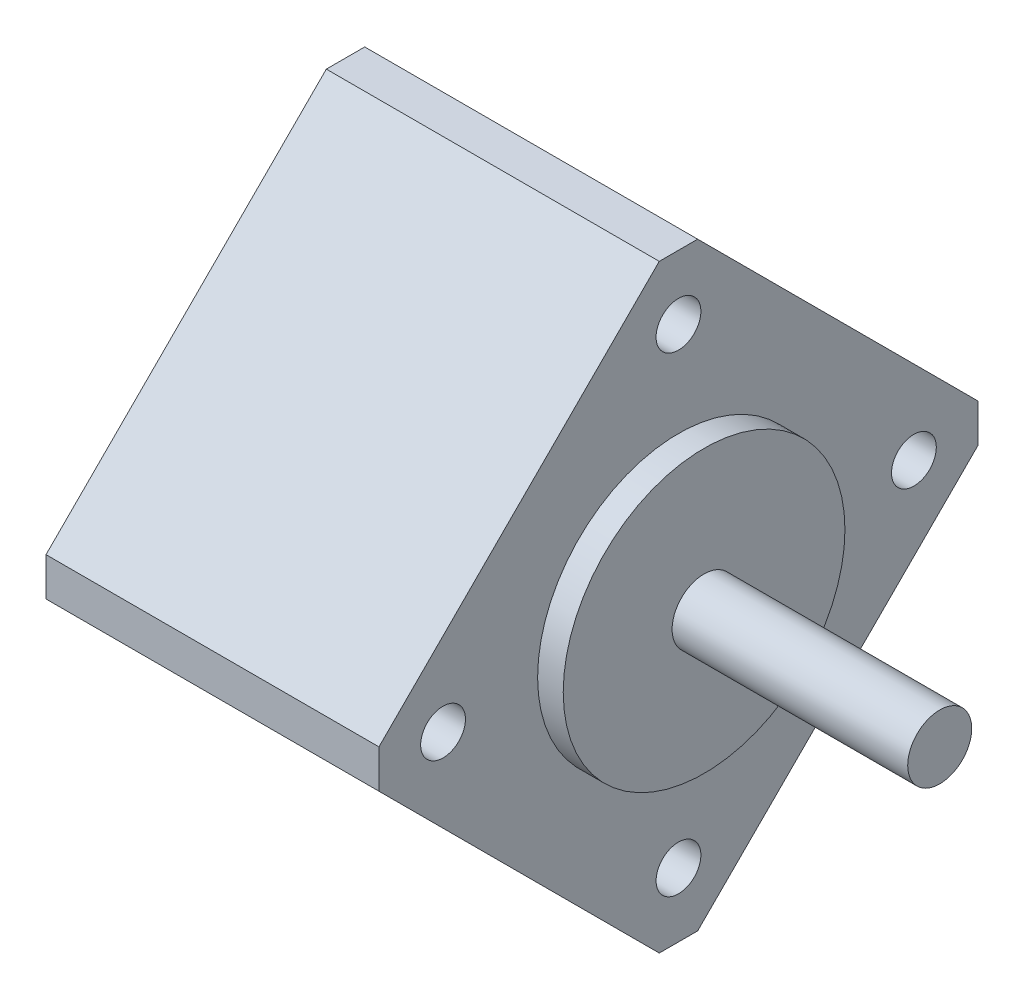
SolidWorks part; units mm, degrees
ref_plane "Front Plane" through (0, 0, 0) normal (0, 0, 1) x (1, 0, 0)
ref_plane "Top Plane" through (0, 0, 0) normal (0, 1, 0) x (1, 0, 0)
ref_plane "Right Plane" through (0, 0, 0) normal (1, 0, 0) x (0, 0, -1)
sketch "Sketch1" plane through (0, 0, 0) normal (0, 0, 1) x (1, 0, 0)
  line L0 (0, 0) -> (58.591, 0) construction
  line L2 (0, 0) -> (18.4, 0)
  line L3 (0, 0) -> (0, 2.5)
  line L4 (0, 2.5) -> (18.4, 2.5)
  line L5 (18.4, 0) -> (18.4, 2.5)
  line L6 (6, 2.5) -> (6, 6)
  line L11 (6, 6) -> (9.97, 6)
  line L16 (12.97, 6) -> (12.97, 3)
  line L17 (12.97, 3) -> (13.6304, 3)
  line L18 (13.6304, 3) -> (13.6304, 2.5)
  line L19 (13.6304, 2.5) -> (6, 2.5)
  line L22 (13.6304, 2.5) -> (16.1104, 2.5)
  line L23 (13.6304, 2.5) -> (13.6304, 4)
  line L24 (13.6304, 4) -> (16.1104, 4)
  line L25 (16.1104, 2.5) -> (16.1104, 4)
  line L27 (6, 6) -> (9.97, 6)
  line L28 (6, 6) -> (6, 9)
  line L29 (6, 9) -> (9.97, 9)
  line L30 (9.97, 6) -> (9.97, 9)
  line L31 (6, 9) -> (6, 8.25)
  line L32 (6, 8.25) -> (5, 8.25)
  line L33 (8.58, 22.001) -> (8.58, 12.476) construction
  line L34 (5, 12.476) -> (12.16, 12.476)
  line L35 (9.97, 9) -> (12.16, 9)
  line L36 (5, 7.5) -> (3, 7.5)
  line L37 (5, 8.25) -> (5, 12.476)
  line L38 (5, 7.5) -> (5, 14)
  line L39 (5, 14) -> (3, 14)
  line L40 (3, 7.5) -> (3, 14)
  line L41 (5, 22.001) -> (12.16, 22.001)
  line L42 (5, 22.001) -> (5, 30.1625)
  line L43 (5, 30.1625) -> (12.16, 30.1625)
  line L44 (12.16, 22.001) -> (12.16, 30.1625)
  line L49 (16.6304, 22.001) -> (16.6304, 7.5)
  line L51 (23.0104, 7.5) -> (23.0104, 6.5)
  line L54 (16.1104, 4) -> (13.6304, 4)
  line L56 (18.0304, 7.5) -> (23.0104, 7.5)
  line L57 (13.16, 22.001) -> (16.6304, 22.001)
  line L58 (16.1104, 3.5) -> (20.0104, 3.5)
  line L59 (29.9004, 14) -> (26.9004, 11)
  line L60 (4, 31.75) -> (18.0304, 31.75)
  line L61 (18.0304, 7.5) -> (23.0104, 7.5)
  line L62 (18.0304, 7.5) -> (18.0304, 12)
  line L63 (18.0304, 12) -> (23.0104, 12)
  line L64 (23.0104, 7.5) -> (23.0104, 12)
  line L65 (18.0304, 31.75) -> (18.0304, 12)
  line L66 (23.0104, 11) -> (26.9004, 11)
  line L67 (34.8004, 23) -> (31.3004, 19.5)
  line L68 (35.8004, 31) -> (38.7904, 33.99)
  line L69 (29.9004, 14) -> (29.9004, 15)
  line L70 (29.9004, 15) -> (22.9304, 15)
  line L71 (22.9304, 15) -> (21.0304, 15)
  line L72 (18.0304, 7.5) -> (16.6304, 7.5)
  line L73 (21.0304, 15) -> (21.0304, 43)
  line L74 (20.0304, 40) -> (10.0704, 40)
  line L75 (10.0704, 40) -> (4, 40)
  line L76 (21.0304, 43) -> (20.0304, 43)
  line L77 (22.9304, 15) -> (29.9004, 15)
  line L78 (22.9304, 15) -> (22.9304, 21)
  line L79 (22.9304, 21) -> (29.9004, 21)
  line L80 (29.9004, 15) -> (29.9004, 21)
  line L81 (10.0704, 40) -> (20.0304, 40)
  line L82 (10.0704, 40) -> (10.0704, 50)
  line L83 (10.0704, 50) -> (20.0304, 50)
  line L84 (20.0304, 40) -> (20.0304, 50)
  line L85 (4, 40) -> (4, 31.75)
  line L86 (12.97, 3) -> (12.97, 2.5)
  line L87 (31.3004, 19.5) -> (29.9004, 19.5)
  line L88 (21.51, 63.5) -> (21.51, 44)
  line L89 (21.51, 63.5) -> (25.9304, 63.5)
  line L90 (25.9304, 63.5) -> (25.9304, 25)
  line L91 (27.8304, 25) -> (25.9304, 25)
  line L92 (10.0704, 48) -> (9, 48)
  line L93 (9, 48) -> (9, 53.476)
  line L94 (9, 53.476) -> (20.0304, 53.476)
  line L95 (20.0304, 53.476) -> (20.0304, 50)
  line L96 (14.5152, 63.001) -> (14.5152, 53.476) construction
  line L97 (9, 63.001) -> (20.0304, 63.001)
  line L98 (9, 63.001) -> (9, 68.2625)
  line L99 (9, 68.2625) -> (20.0304, 68.2625)
  line L100 (20.0304, 63.001) -> (20.0304, 68.2625)
  line L101 (12.97, 6) -> (11.97, 6)
  line L102 (9, 42.5) -> (5, 42.5)
  line L103 (9, 42.5) -> (9, 55)
  line L104 (9, 55) -> (5, 55)
  line L105 (5, 42.5) -> (5, 55)
  line L106 (9.97, 6) -> (10.87, 6)
  line L107 (27.8304, 25) -> (34.8004, 25)
  line L108 (34.8004, 25) -> (34.8004, 23)
  line L109 (0, 0) -> (-2, 0)
  line L110 (0, 0) -> (0, 11)
  line L111 (27.8304, 25) -> (34.8004, 25)
  line L112 (27.8304, 25) -> (27.8304, 32.5)
  line L113 (27.8304, 32.5) -> (34.8004, 32.5)
  line L114 (34.8004, 25) -> (34.8004, 32.5)
  line L115 (35.8004, 31) -> (34.8004, 31)
  line L116 (27.8304, 32.5) -> (27.8304, 64.5)
  line L117 (21.1827, 74.025) -> (6.8477, 74.025)
  line L118 (6.8477, 74.025) -> (6.8477, 76.2)
  line L119 (38.7904, 47.29) -> (30.8304, 55.25)
  line L120 (0, 11) -> (-2, 11)
  line L121 (38.7904, 43.815) -> (30.8529, 43.815)
  line L123 (-4.8, 69.85) -> (1.55, 76.2)
  line L124 (38.7904, 47.29) -> (38.7904, 33.99)
  line L125 (-2, 0) -> (-2, 11)
  line L126 (38.7904, 37.465) -> (30.8529, 37.465)
  line L127 (30.8529, 43.815) -> (30.8529, 37.465)
  line L128 (6, 2.5) -> (6, 0)
  line L129 (0, 63.5) -> (0, 30)
  line L132 (5, 63.5) -> (0, 63.5)
  line L136 (-1.8, 30) -> (-11.76, 30)
  line L138 (-13.76, 25.4) -> (-2, 25.4)
  line L139 (-2, 25.4) -> (-2, 11.5)
  line L140 (27.8304, 64.5) -> (21.1827, 64.5)
  line L141 (-1.8, 30) -> (-11.76, 30)
  line L142 (-1.8, 30) -> (-1.8, 39)
  line L143 (-1.8, 39) -> (-11.76, 39)
  line L144 (-11.76, 30) -> (-11.76, 39)
  line L145 (21.1827, 64.5) -> (21.1827, 74.025)
  line L146 (-12.76, 37) -> (-12.76, 47.29)
  line L147 (-12.76, 37) -> (-11.76, 37)
  line L148 (30.8304, 55.25) -> (30.8304, 76.2)
  line L149 (11.97, 6) -> (11.97, 5.45)
  line L154 (-2, 11.5) -> (1, 11.5)
  line L155 (5, 60.6197) -> (24.05, 60.6197)
  line L160 (5, 60.6197) -> (5, 55.8572)
  line L161 (5, 55.8572) -> (24.05, 55.8572)
  line L166 (24.05, 60.6197) -> (24.05, 55.8572)
  line L167 (5, 60.6197) -> (24.05, 55.8572) construction
  line L172 (5, 55.8572) -> (24.05, 60.6197) construction
  line L173 (24.05, 62.2072) -> (25.9304, 62.2072)
  line L174 (11.97, 5.45) -> (10.87, 5.45)
  line L175 (10.87, 6) -> (10.87, 5.45)
  line L176 (24.05, 62.2072) -> (24.05, 54.2697)
  line L177 (24.05, 54.2697) -> (25.9304, 54.2697)
  line L178 (25.9304, 62.2072) -> (25.9304, 54.2697)
  line L179 (24.05, 62.2072) -> (25.9304, 54.2697) construction
  line L180 (24.05, 54.2697) -> (25.9304, 62.2072) construction
  line L181 (3, 19.6197) -> (15.7, 19.6197)
  line L182 (3, 19.6197) -> (3, 14.8572)
  line L183 (3, 14.8572) -> (15.7, 14.8572)
  line L184 (15.7, 19.6197) -> (15.7, 14.8572)
  line L185 (3, 19.6197) -> (15.7, 14.8572) construction
  line L186 (3, 14.8572) -> (15.7, 19.6197) construction
  line L187 (15.7, 21.2072) -> (16.6304, 21.2072)
  line L188 (15.7, 21.2072) -> (15.7, 13.2697)
  line L189 (15.7, 13.2697) -> (16.6304, 13.2697)
  line L190 (16.6304, 21.2072) -> (16.6304, 13.2697)
  line L191 (15.7, 21.2072) -> (16.6304, 13.2697) construction
  line L192 (15.7, 13.2697) -> (16.6304, 21.2072) construction
  line L193 (1, 11.5) -> (1, 6.5)
  line L194 (1, 6.5) -> (3, 6.5)
  line L195 (23.0104, 6.5) -> (20.0104, 3.5)
  line L196 (5, 63.5) -> (5, 42.5)
  line L197 (5, 42.5) -> (3, 42.5)
  line L198 (3, 42.5) -> (3, 6.5)
  line L199 (6, 0) -> (12.97, 0)
  line L200 (12.97, 0) -> (12.97, 2.5)
  line L201 (18.0304, 31.75) -> (18.0304, 35.875)
  line L202 (18.0304, 35.875) -> (21.0304, 35.875)
  line L203 (30.8304, 76.2) -> (6.8477, 76.2)
  line L204 (3.4027, 69.85) -> (7.8477, 69.85) construction
  line L205 (7.8477, 67.4687) -> (26.8977, 67.4688)
  line L206 (7.8477, 74.025) -> (7.8477, 64.5)
  line L207 (7.8477, 64.5) -> (-1.8, 64.5)
  line L208 (-1.8, 64.5) -> (-1.8, 39)
  line L209 (-12.76, 47.29) -> (-4.8, 55.25)
  line L210 (-4.8, 55.25) -> (-4.8, 69.85)
  line L211 (7.8477, 67.4687) -> (7.8477, 72.2313)
  line L212 (7.8477, 72.2313) -> (26.8977, 72.2313)
  line L213 (26.8977, 67.4688) -> (26.8977, 72.2313)
  line L214 (26.8977, 73.8187) -> (30.8304, 73.8187)
  line L215 (26.8977, 73.8187) -> (26.8977, 65.8813)
  line L216 (26.8977, 65.8813) -> (30.8304, 65.8813)
  line L217 (30.8304, 73.8187) -> (30.8304, 65.8813)
  line L218 (3.4027, 72.2313) -> (25.6277, 72.2313)
  line L219 (3.4027, 72.2313) -> (3.4027, 67.4687)
  line L220 (3.4027, 67.4687) -> (25.6277, 67.4687)
  line L221 (25.6277, 72.2313) -> (25.6277, 67.4687)
  line L222 (25.6277, 69.85) -> (21.1827, 69.85) construction
  line L223 (21.51, 44) -> (22.9304, 44)
  line L224 (22.9304, 44) -> (22.9304, 21)
  line L225 (13.6304, 4) -> (13.6304, 12.2697)
  line L226 (13.6304, 12.2697) -> (13.16, 12.2697)
  line L227 (13.16, 12.2697) -> (13.16, 22.001)
  line L228 (12.16, 9) -> (12.16, 12.476)
  line L229 (-1.8, 30) -> (0, 30)
  line L230 (9, 65.6317) -> (3.4027, 65.6317) construction
  line L231 (20.0304, 65.6317) -> (25.6277, 65.6317) construction
  line L232 (1.55, 76.2) -> (6.8477, 76.2)
  line L233 (-11.76, 30) -> (-13.76, 30)
  line L234 (-13.76, 30) -> (-13.76, 25.4)
  circle A0 centre (26.8804, 25.95) radius 0.95
  circle A1 centre (21.9804, 15.95) radius 0.95
  circle A2 centre (17.3304, 8.2) radius 0.7
  circle A3 centre (10.42, 6.45) radius 0.45
  circle A4 centre (-0.9, 30.9) radius 0.9
  point P7 (24.9902, 58.2385)
  point P131 (16.1652, 17.2385)
  point P135 (14.525, 58.2385)
  point P146 (9.35, 17.2385)
sketch "Sketch2" plane through (0, 0, 0) normal (0, 0, 1) x (1, 0, 0)
  line L0 (0, 0) -> (-2, 0) construction
  line L1 (0, 11) -> (-2, 11) construction
  line L2 (-2, 0) -> (-2, 11) construction
  line L3 (0, 0) -> (0, 11) construction
  line L4 (18.4, 0) -> (18.4, 2.5) construction
  line L5 (0, 0) -> (18.4, 0) construction
  line L6 (0, 2.5) -> (18.4, 2.5) construction
  line L7 (0, 0) -> (-2, 0)
  line L8 (0, 11) -> (-2, 11)
  line L9 (-2, 0) -> (-2, 11)
  line L10 (0, 0) -> (0, 11)
  line L11 (18.4, 0) -> (18.4, 2.5)
  line L12 (0, 0) -> (18.4, 0)
  line L13 (0, 2.5) -> (18.4, 2.5)
revolve "Revolve1" add sketch "Sketch2" angle 360 about L0 region at (-1, 5.5, 0) region at (9.2, 1.25, 0)
sketch "Sketch3" plane through (-2, 0, 0) normal (-1, 0, 0) x (0, 0, 1)
  line L0 (0, 23.3902) -> (1.5, 23.3902)
  line L1 (1.5, 23.3902) -> (23.3902, 1.5)
  line L2 (23.3902, 1.5) -> (23.3902, 0)
  line L3 (23.3902, -1.5) -> (1.5, -23.3902)
  line L4 (1.5, -23.3902) -> (0, -23.3902)
  line L5 (23.3902, 0) -> (23.3902, -1.5)
  line L6 (-1.5, -23.3902) -> (-23.3902, -1.5)
  line L7 (-23.3902, -1.5) -> (-23.3902, 0)
  line L8 (0, -23.3902) -> (-1.5, -23.3902)
  line L9 (-23.3902, 1.5) -> (-1.5, 23.3902)
  line L10 (-1.5, 23.3902) -> (0, 23.3902)
  line L11 (-23.3902, 0) -> (-23.3902, 1.5)
  circle A0 centre (0, 18.3848) radius 1.75
  circle A1 centre (18.3848, 0) radius 1.75
  circle A2 centre (0, -18.3848) radius 1.75
  circle A3 centre (-18.3848, 0) radius 1.75
  point P19 (0, 0)
  point P25 (0, 0)
  dimension "D5" = 3.5
  dimension "D2" = 35.2
  dimension "D3" = 3
  dimension "D6" = 26
  dimension "D1" = 4
  dimension "D4" = 4
extrude "Boss-Extrude1" add sketch "Sketch3" along normal blind 26
